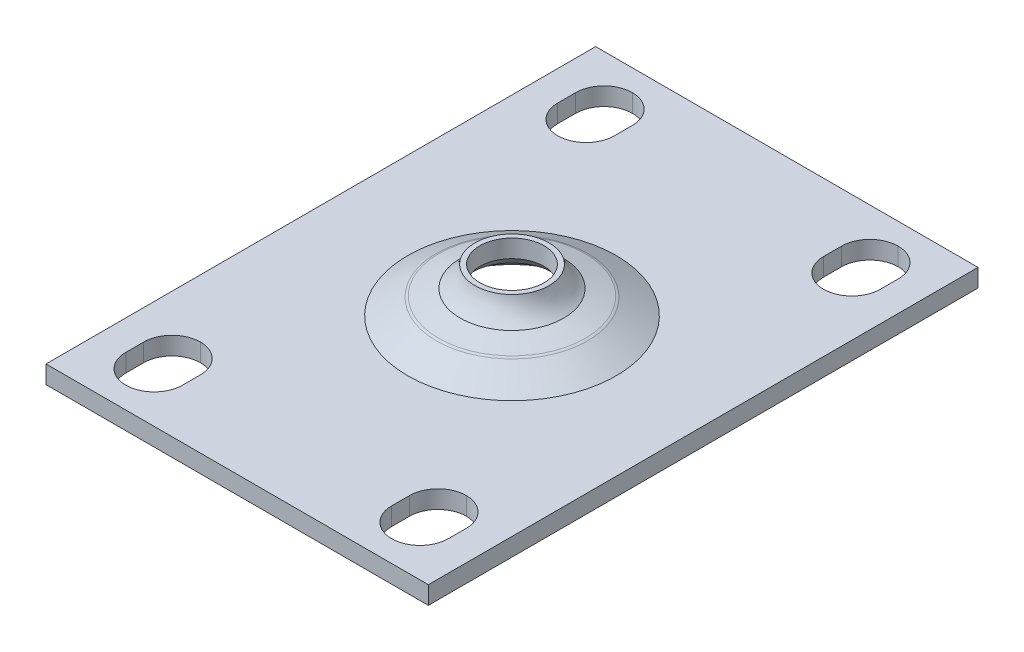
SolidWorks part; units mm, degrees
material "AISI 1020"
ref_plane "Front Plane" through (0, 0, 0) normal (0, 0, 1) x (1, 0, 0)
ref_plane "Top Plane" through (0, 0, 0) normal (0, 1, 0) x (1, 0, 0)
ref_plane "Right Plane" through (0, 0, 0) normal (1, 0, 0) x (0, 0, -1)
sketch "Sketch1" plane through (0, 0, 0) normal (0, 1, 0) x (1, 0, 0)
  line L1 (32, 46) -> (-32, 46)
  line L2 (32, 46) -> (32, -46)
  line L3 (32, -46) -> (-32, -46)
  line L4 (-32, 46) -> (-32, -46)
  dimension "D1" = 92
  dimension "D2" = 64
  dimension "D3" = 32
  dimension "D4" = 46
extrude "Boss-Extrude1" add sketch "Sketch1" along normal blind 3
sketch "Sketch2" plane through (0, 3, 0) normal (0, 1, 0) x (1, 0, 0)
  line L0 (27, 46) -> (27, -46) construction
  line L1 (32, 46) -> (-32, 46) construction
  line L2 (-32, -46) -> (32, -46) construction
  line L3 (32, -46) -> (32, 46) construction
  line L4 (32.8285, 42.4) -> (-42.3475, 42.4) construction
  line L5 (0, 48.9376) -> (0, -49.5478) construction
  line L6 (50.8284, 0) -> (-57.2612, 0) construction
  line L7 (27, 29.9) -> (17.5, 29.9)
  line L8 (27, 29.9) -> (27, 42.4)
  line L9 (27, 42.4) -> (17.5, 42.4)
  line L10 (17.5, 29.9) -> (17.5, 42.4)
  line L11 (-27, 42.4) -> (-17.5, 42.4)
  line L12 (-17.5, 29.9) -> (-17.5, 42.4)
  line L13 (-27, 29.9) -> (-17.5, 29.9)
  line L14 (-27, 29.9) -> (-27, 42.4)
  line L15 (27, -42.4) -> (17.5, -42.4)
  line L16 (17.5, -29.9) -> (17.5, -42.4)
  line L17 (27, -29.9) -> (17.5, -29.9)
  line L18 (27, -29.9) -> (27, -42.4)
  line L19 (-27, -29.9) -> (-27, -42.4)
  line L20 (-27, -29.9) -> (-17.5, -29.9)
  line L21 (-17.5, -29.9) -> (-17.5, -42.4)
  line L22 (-27, -42.4) -> (-17.5, -42.4)
  dimension "D1" = 5
  dimension "D2" = 3.6
  dimension "D3" = 9.5
  dimension "D4" = 12.5
extrude "Cut-Extrude1" cut sketch "Sketch2" against normal up to surface (3 mm away) up to face at (0, 0, 0)
fillet "Fillet1" radius 4.75 16 edges at (27, 1.5, 42.4) (17.5, 1.5, 42.4) (17.5, 1.5, 29.9) (27, 1.5, 29.9) (-27, 1.5, 42.4) (-17.5, 1.5, 42.4) (-17.5, 1.5, 29.9) (-27, 1.5, 29.9) (27, 1.5, -29.9) (17.5, 1.5, -29.9) (27, 1.5, -42.4) (17.5, 1.5, -42.4) (-17.5, 1.5, -29.9) (-27, 1.5, -29.9) (-17.5, 1.5, -42.4) (-27, 1.5, -42.4)
sketch "Sketch5" plane through (0, 0, 0) normal (1, 0, 0) x (0, 0, -1)
  line L0 (0, -11.8428) -> (0, 38.1572) construction
  line L1 (12.48, 22.7187) -> (12.48, -11.8428) construction
  line L2 (17.443, 22.7187) -> (17.443, -11.8428) construction
  line L3 (-46.1514, 5.785) -> (46.287, 5.785) construction
  line L4 (2, 14.8258) -> (2, -2.5666) construction
  line L10 (8.652, 22.7187) -> (8.652, -11.8428) construction
  line L11 (-25.69, 6.959) -> (49.758, 6.959) construction
  line L12 (-27.52, 10.454) -> (47.928, 10.454) construction
  line L13 (6.205, 22.7187) -> (6.205, -11.8428) construction
  line L27 (46, 3) -> (46, 0) construction
  line L28 (-46, 3) -> (46, 3) construction
  line L29 (46, 3) -> (17.443, 3) construction
  line L30 (17.443, 3) -> (12.48, 5.785)
  line L31 (17.443, 3) -> (13.3561, 3) construction
  line L32 (17.443, 3) -> (17.443, 5.785) construction
  line L33 (17.443, 5.785) -> (12.48, 5.785) construction
  line L34 (12.48, 3) -> (12.48, 5.785) construction
  line L35 (12.48, 5.785) -> (8.652, 5.785) construction
  line L36 (12.48, 5.785) -> (12.48, 6.959) construction
  line L37 (12.48, 6.959) -> (8.652, 6.959) construction
  line L38 (8.652, 5.785) -> (8.652, 6.959) construction
  line L39 (8.652, 6.959) -> (6.205, 6.959) construction
  line L40 (8.652, 6.959) -> (8.652, 10.454) construction
  line L41 (8.652, 10.454) -> (6.205, 10.454) construction
  line L42 (6.205, 6.959) -> (6.205, 10.454) construction
  line L43 (12.48, 5.785) -> (8.652, 6.959)
  line L46 (0, 10.454) -> (6.205, 10.454)
  line L47 (13.3561, 3) -> (11.6884, 3.9358)
  line L48 (11.6884, 3.9358) -> (7.8064, 5.1264)
  line L49 (17.443, 3) -> (13.3561, 3)
  line L50 (16.4643, 1.2558) -> (11.6884, 3.9358) construction
  line L51 (0, 10.454) -> (0, 3)
  line L52 (0, 8.454) -> (4.8058, 8.454) construction
  line L53 (4.8058, 8.454) -> (2, 8.454)
  line L54 (2, 8.454) -> (2, 3)
  line L55 (2, 3) -> (0, 3)
  arc A1 (8.652, 6.959) -> (6.205, 10.454) centre (11.9136, 11.8467) cw
  arc A2 (7.8064, 5.1264) -> (4.8058, 8.454) centre (11.9136, 11.8467) cw
  dimension "D9" = 5.876
  dimension "D1" = 28.557
  dimension "D2" = 4.963
  dimension "D3" = 3.828
  dimension "D4" = 2.447
  dimension "D5" = 2.785
  dimension "D6" = 1.174
  dimension "D7" = 3.495
  dimension "D8" = 50
  dimension "D11" = 2
  dimension "D10" = 2
revolve "Revolve1" add sketch "Sketch5" angle 360 about L0
fillet "Fillet2" radius 2 1 edges at (0, 5.785, -12.48)
sketch "Sketch6" plane through (0, 10.454, 0) normal (0, 1, 0) x (1, 0, 0)
  circle A0 centre (0, 0) radius 5.375
  dimension "D1" = 10.75
extrude "Cut-Extrude2" cut sketch "Sketch6" against normal up to surface (10.454 mm away) up to face at (-22.25, 0, -36.15)
ref_plane "Plane1" through (0, 0, 0) normal (0, -1, 0) x (-1, 0, 0)
sketch "Sketch8" plane through (0, 0, 0) normal (0, -1, 0) x (-1, 0, 0)
  circle A1 centre (0, 0) radius 13.3561
  circle A2 centre (0, 0) radius 13.3561
  dimension "D1" = 0
extrude "Cut-Extrude3" cut sketch "Sketch8" against normal up to surface (3 mm away) up to face at (0, 3, -5.375)
fillet "Fillet3" radius 2 1 edges at (0, 3, -13.3561)
fillet "Fillet4" radius 2 1 edges at (0, 0, -13.3561)
